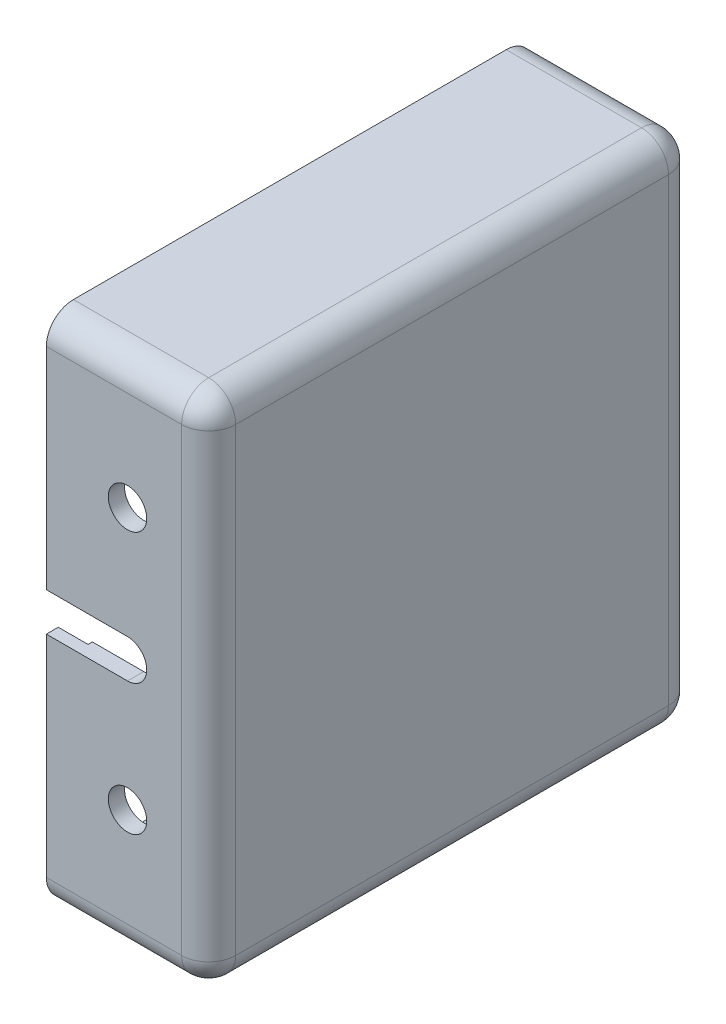
SolidWorks part; units mm, degrees
ref_plane "Front Plane" through (0, 0, 0) normal (1, 0, 0) x (0, 1, 0)
ref_plane "Top Plane" through (0, 0, 0) normal (0, 0, 1) x (0, 1, 0)
ref_plane "Right Plane" through (0, 0, 0) normal (0, 1, 0) x (-1, 0, 0)
sketch "Sketch1" plane through (0, 0, 0) normal (0, 0, 1) x (0, 1, 0)
  line L1 (-47.5, -15) -> (47.5, -15)
  line L2 (-47.5, -15) -> (-47.5, 15)
  line L3 (-47.5, 15) -> (47.5, 15)
  line L4 (47.5, -15) -> (47.5, 15)
  line L5 (-47.5, -15) -> (47.5, 15) construction
  line L6 (-47.5, 15) -> (47.5, -15) construction
  line L7 (0, 15) -> (0, -15) construction
  circle A0 centre (0, 0) radius 3
  point P0 (0, 0)
  dimension "D3" = 6
  dimension "D1" = 30
  dimension "D2" = 95
extrude "30 x 95 x 90" add sketch "Sketch1" along normal blind 90 contours L1 L4 L3 L2 A0 | A0 region at (0, -46.5038, 0) region at (0, 0, 0)
shell "2 mm top/bot 3 mm side" thickness 3 removed face at (-15, 0, 45)
sketch "Sketch3" plane through (0, 0, 0) normal (0, 0, -1) x (1, 0, 0)
  line L0 (0, 47.5) -> (0, -47.5) construction
  line L1 (15, 47.5) -> (-15, 47.5) construction
  line L2 (15, -47.5) -> (-15, -47.5) construction
  line L4 (0, -47.5) -> (0, -27.5)
  line L5 (0, 47.5) -> (0, 37.5)
  circle A0 centre (0, 32.5) radius 5
  circle A4 centre (0, 12.5) radius 5
  circle A5 centre (0, -7.5) radius 5
  circle A6 centre (0, -27.5) radius 5
  dimension "D1" = 10
  dimension "D3" = 10
  dimension "D2" = 4
sketch "Sketch4" plane through (0, 0, 90) normal (0, 0, 1) x (1, 0, 0)
  line L0 (0, 47.5) -> (0, -47.5) construction
  line L1 (15, 47.5) -> (-15, 47.5) construction
  line L2 (15, -47.5) -> (-15, -47.5) construction
  line L3 (0, 3.55) -> (0, 20.65)
  line L4 (-15, 0) -> (15, 0) construction
  line L5 (-15, -47.5) -> (-15, 47.5) construction
  line L6 (15, -47.5) -> (15, 47.5) construction
  line L7 (0, 3.55) -> (-15, 3.55)
  line L8 (0, -3.55) -> (-15, -3.55)
  line L9 (-15, -3.55) -> (-15, 3.55)
  circle A0 centre (0, 0) radius 3.55
  circle A1 centre (0, 24.2) radius 3.55
  circle A2 centre (0, -24.2) radius 3.55
  line M6 (-15, 47.5) -> (-15, -47.5)
  dimension "D1" = 7.1
  dimension "D2" = 17.1
extrude "7.1 mm fixture holes" cut sketch "Sketch4" along direction (0, 0, 1) on the side against the normal blind 10 contours A1 | A0 | A2 | A0 L7 L8 M6 region at (0, 24.2, 90) region at (-8.8684, 0, 90) region at (0, 0, 90) region at (0, -24.2, 90)
fillet "5 mm radius" radius 5 16 edges at (12, 42.5, 45) (12, -42.5, 45) (15, -47.5, 45) (15, 47.5, 45) (-1.5, 42.5, 87) (-1.5, -42.5, 87) (15, 0, 90) (15, 0, 0) (12, 0, 3) (-1.5, -42.5, 3) (-1.5, 42.5, 3) (12, 0, 87) (0, 47.5, 90) (0, 47.5, 0) (0, -47.5, 0) (0, -47.5, 90)
extrude "4x 10 mm port" cut sketch "Sketch3" against normal blind 10 contours A0 L0 | L0 A0 | A4 L0 | L0 A4 | A5 L0 | L0 A5 | L0 A6 L4 | A6 L0 L4 region at (2.1221, -32.5, 0) region at (2.1221, 27.5, 0) region at (-2.1221, 27.5, 0) region at (2.1221, 7.5, 0) region at (-2.1221, 7.5, 0) region at (2.1221, -12.5, 0) region at (-2.1221, -12.5, 0) region at (-2.1221, -32.5, 0)
sketch "Sketch5" plane through (0, 0, 0) normal (0, 0, -1) x (1, 0, 0)
  line L0 (-15, 41) -> (-14, 41)
  line L1 (-15, 42.5) -> (-15, -42.5) construction
  line L2 (-14, 41) -> (-14, 43)
  line L8 (-9.5, -43) -> (-9.5, 43)
  line L9 (10, 0) -> (-12, 0) construction
  line L10 (10, -42.5) -> (10, 42.5) construction
  line L12 (-15, 0) -> (-15, -41)
  line L15 (-14, 43) -> (-9.5, 43)
  line L16 (-13, -41) -> (-13, -43)
  line L18 (-15, 0) -> (-15, 41)
  line L21 (-13, -43) -> (-12, -43)
  line L23 (-12, 43) -> (-9.5, 43)
  line L24 (-12, -43) -> (-9.5, -43)
  line L25 (-15, -41) -> (-13, -41)
  point P7 (-9.5, 0)
  point P13 (-12, 0)
  line M5 (-15, 42.5) -> (-15, -42.5)
  line M6 (-15, -42.5) -> (10, -42.5)
  line M8 (10, 42.5) -> (-15, 42.5)
  dimension "D2" = 1
  dimension "D3" = 41
  dimension "D4" = 2
  dimension "D5" = 41
extrude "Cut-Extrude2" cut sketch "Sketch5" against normal offset from surface (87.8 mm away) 0.8 contours L25 L16 L8 L2 L0 M5 M6 M8 region at (-12.2314, -0.1353, 0) up to face at (3.55, 24.2, 87) offset beyond the face yes
chamfer "Chamfer2" distance 1.5 angle 45 4 edges at (-13, 42.5, 84.9) (-13, 42.5, 4) (-14, -42.5, 84.9) (-14, -42.5, 4)
